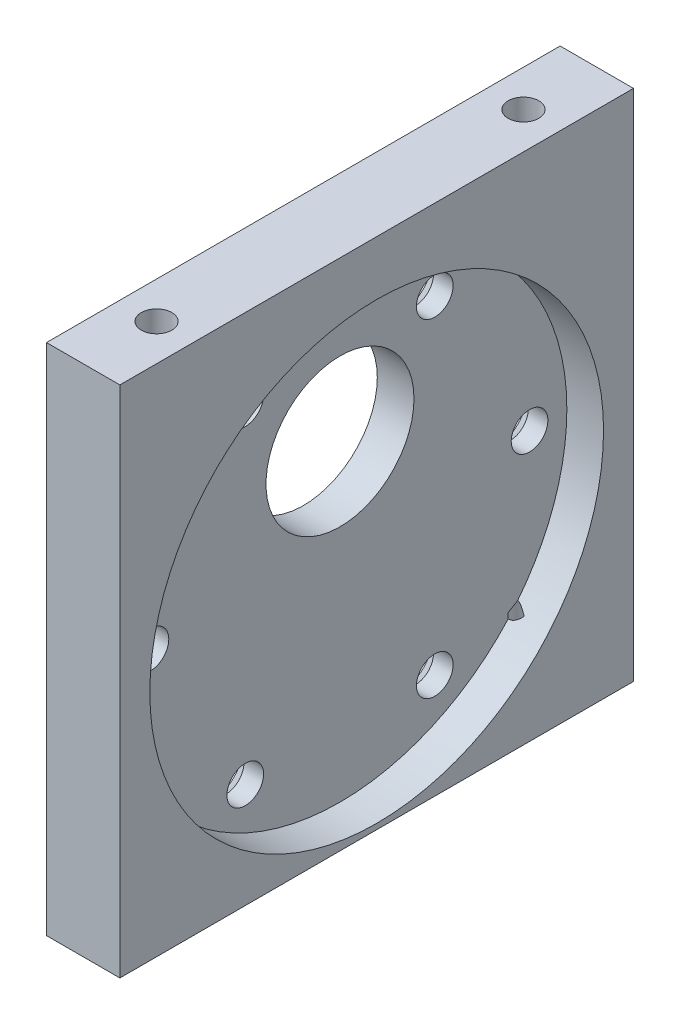
SolidWorks part; units mm, degrees
material "1060 Alloy"
ref_plane "Front Plane" through (0, 0, 0) normal (0, 0, 1) x (1, 0, 0)
ref_plane "Top Plane" through (0, 0, 0) normal (0, 1, 0) x (1, 0, 0)
ref_plane "Right Plane" through (0, 0, 0) normal (1, 0, 0) x (0, 0, -1)
sketch "Sketch1" plane through (0, 0, 0) normal (0, 1, 0) x (1, 0, 0)
  line L1 (0, 0) -> (6, 0)
  line L2 (0, 0) -> (0, 42)
  line L3 (0, 42) -> (6, 42)
  line L4 (6, 0) -> (6, 42)
  dimension "D1" = 42
  dimension "D2" = 6
extrude "Boss-Extrude1" add sketch "Sketch1" along normal blind 42
hole_wizard "Tap Drill for M3 Tap1" positions "Sketch3" profile "Sketch2" hole size "M3" standard "ISO"
sketch "Sketch3" plane through (0, 42, 0) normal (0, 1, 0) x (-1, 0, 0)
  line L0 (0, 0) -> (-6, 0) construction
  line L1 (-6, 0) -> (-6, -42) construction
  line L2 (-6, -42) -> (0, -42) construction
  point P0 (-3, -6)
  point P1 (-3, -36)
  point P6 (-3, -42)
  dimension "D1" = 6
  dimension "D2" = 3
  dimension "D3" = 6
sketch "Sketch2" plane through (3, 42, -6) normal (1, 0, 0) x (0, 0, 1)
  line L0 (0, 0) -> (0, 10.7511)
  line L1 (0, 10.7511) -> (1.25, 10)
  line L2 (1.25, 10) -> (1.25, 0)
  line L5 (1.25, 0) -> (0, 0)
  line L10 (0, 10.7511) -> (-1.25, 10) construction
  line L11 (0, -6.35) -> (0, 107.95) construction
  dimension "Hole Dia." = 2.5
  dimension "Hole Depth" = 10
  dimension "Drill Angle" = 118
hole_wizard "Tap Drill for M3 Tap2" positions "Sketch5" profile "Sketch4" hole size "M3" standard "ISO"
sketch "Sketch5" plane through (0, 0, 0) normal (0, -1, 0) x (1, 0, 0)
  line L0 (6, 0) -> (6, -42) construction
  line L1 (0, 0) -> (6, 0) construction
  line L2 (6, -42) -> (0, -42) construction
  point P0 (3, -6)
  point P1 (3, -36)
  dimension "D1" = 3
  dimension "D2" = 6
  dimension "D3" = 6
sketch "Sketch4" plane through (3, 0, -6) normal (1, 0, 0) x (0, 0, -1)
  line L0 (0, 0) -> (0, 7.7511)
  line L1 (0, 7.7511) -> (1.25, 7)
  line L2 (1.25, 7) -> (1.25, 0)
  line L5 (1.25, 0) -> (0, 0)
  line L10 (0, 7.7511) -> (-1.25, 7) construction
  line L11 (0, -6.35) -> (0, 107.95) construction
  dimension "Hole Dia." = 2.5
  dimension "Hole Depth" = 7
  dimension "Drill Angle" = 118
sketch "Sketch6" plane through (6, 0, 0) normal (1, 0, 0) x (0, 0, -1)
  line L0 (0, 42) -> (0, 0) construction
  line L1 (0, 0) -> (42, 0) construction
  circle A0 centre (21, 19) radius 18.55
  dimension "D2" = 37.1
  dimension "D1" = 21
  dimension "D3" = 19
extrude "Cut-Extrude1" cut sketch "Sketch6" against normal blind 3
sketch "Sketch7" plane through (3, 0, 0) normal (1, 0, 0) x (0, 0, -1)
  line L1 (2.45, 19) -> (21, 19) construction
  circle A0 centre (21, 26) radius 6.05
  circle A1 centre (21, 19) radius 18.55 construction
  circle A3 centre (5.5, 19) radius 1.5
  circle A4 centre (21, 19) radius 18.55 construction
  dimension "D1" = 12.1
  dimension "D4" = 3
  dimension "D2" = 21
  dimension "D3" = 7
  dimension "D5" = 15.5
extrude "Cut-Extrude2" cut sketch "Sketch7" against normal up to next
pattern_circular "CirPattern1" count 6 over 360 about axis through (6, 19, -21) along (1, 0, 0) of face at (3, 19, -7)
chamfer "Chamfer1" distance 1.4 angle 45 6 edges at (0, 19, -35) (0, 6.8756, -28) (0, 6.8756, -14) (0, 19, -7) (0, 31.1244, -14) (0, 31.1244, -28)
